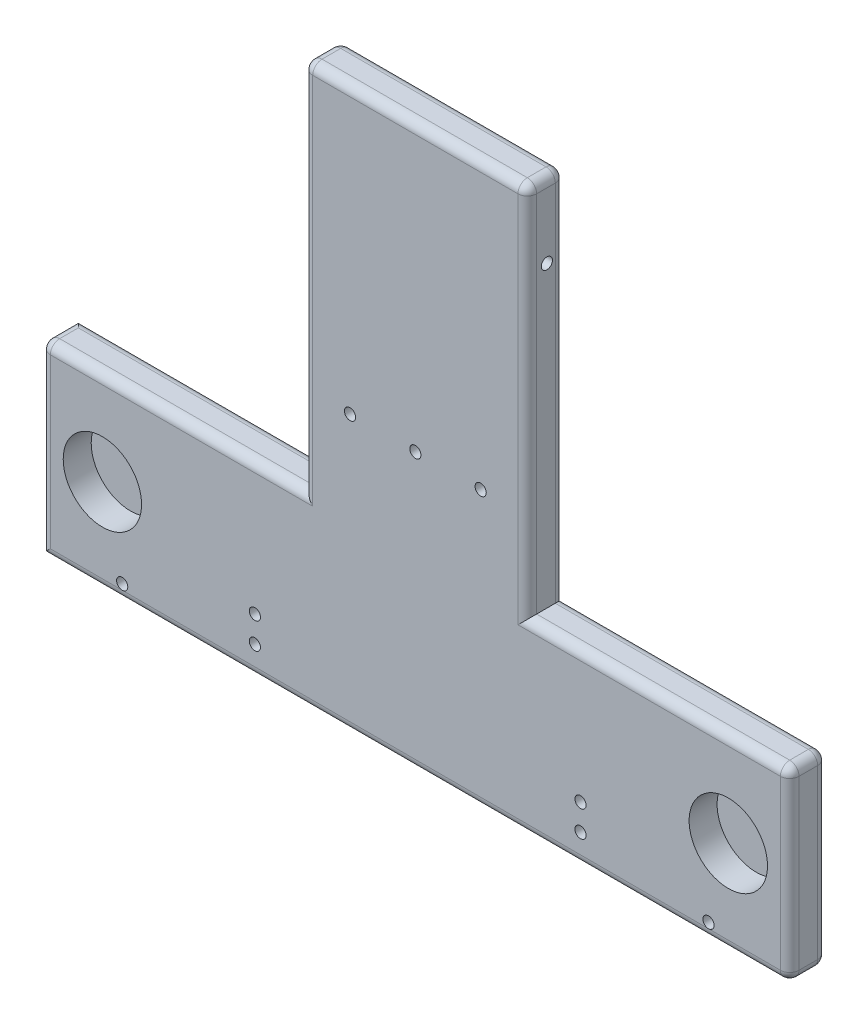
SolidWorks part; units mm, degrees
ref_plane "Front Plane" through (0, 0, 0) normal (0, 0, 1) x (1, 0, 0)
ref_plane "Top Plane" through (0, 0, 0) normal (0, 1, 0) x (1, 0, 0)
ref_plane "Right Plane" through (0, 0, 0) normal (1, 0, 0) x (0, 0, -1)
sketch "Sketch1" plane through (0, 0, 0) normal (0, 0, 1) x (1, 0, 0)
  line L0 (0, 0) -> (0, 190.5941) construction
  line L1 (-200.6, -50) -> (200.6, -50)
  line L2 (-200.6, -50) -> (-200.6, 50)
  line L3 (-200.6, 50) -> (-60, 50)
  line L4 (200.6, -50) -> (200.6, 50)
  line L5 (-200.6, -50) -> (200.6, 50) construction
  line L6 (-200.6, 50) -> (200.6, -50) construction
  line L7 (60, 50) -> (200.6, 50)
  line L8 (-60, 250) -> (60, 250)
  line L9 (-60, 250) -> (-60, 50)
  line L11 (60, 250) -> (60, 50)
  line L12 (-60, 250) -> (60, 50) construction
  line L13 (-60, 50) -> (60, 250) construction
  point P0 (0, 0)
  point P8 (0, 150)
  dimension "D1" = 100
  dimension "D2" = 401.2
  dimension "D3" = 200
  dimension "D4" = 120
extrude "Boss-Extrude1" add sketch "Sketch1" along normal blind 20
sketch "Sketch2" plane through (0, 0, 20) normal (0, 0, 1) x (1, 0, 0)
  line L0 (0, 250) -> (0, -50) construction
  line L1 (60, 250) -> (-60, 250) construction
  line L2 (-200.6, -50) -> (200.6, -50) construction
  line L3 (0, 0) -> (200.6, 0) construction
  line L4 (200.6, -50) -> (200.6, 50) construction
  circle A0 centre (167.7, 0) radius 21
  circle A1 centre (-167.7, 0) radius 21
  dimension "D1" = 42
  dimension "D2" = 167.7
extrude "Cut-Extrude1" cut sketch "Sketch2" against normal blind 15
sketch "Sketch3" plane through (0, 0, 20) normal (0, 0, 1) x (1, 0, 0)
  circle A0 centre (-35, 97.7532) radius 3
  circle A1 centre (35, 97.7532) radius 3
  circle A2 centre (0, 97.7532) radius 3
extrude "Cut-Extrude2" cut sketch "Sketch3" against normal blind 8
cosmetic thread "Cosmetic Thread1" parameters "D2"=10
cosmetic thread "Cosmetic Thread2" parameters "D2"=10
cosmetic thread "Cosmetic Thread3" parameters "D2"=10
sketch "Sketch4" plane through (0, 0, 20) normal (0, 0, 1) x (1, 0, 0)
  circle A0 centre (-86, -20.5) radius 3
  circle A1 centre (88.5, -20.5) radius 3
  circle A2 centre (88.5, -34.5) radius 3
  circle A3 centre (-86, -34.5) radius 3
extrude "Cut-Extrude3" cut sketch "Sketch4" against normal blind 15
cosmetic thread "Cosmetic Thread4" parameters "D2"=10
cosmetic thread "Cosmetic Thread5" parameters "D2"=10
cosmetic thread "Cosmetic Thread6" parameters "D2"=10
cosmetic thread "Cosmetic Thread7" parameters "D2"=10
sketch "Sketch5" plane through (0, 0, 20) normal (0, 0, 1) x (1, 0, 0)
  line L0 (167.7, 0) -> (167.6, -20.9998) construction
  line L1 (-200.6, -50) -> (200.6, -50) construction
  line L2 (167.7, 0) -> (160.0879, -42) construction
  line L3 (167.6, -20.9998) -> (200.6, -20.9998) construction
  line L4 (200.6, -50) -> (200.6, 50) construction
  circle A1 centre (157.0879, -42) radius 3
  circle A2 centre (167.7, 0) radius 21 construction
  dimension "D1" = 6
  dimension "D4" = 10
  dimension "D2" = 20.9998
  dimension "D3" = 8
extrude "Cut-Extrude4" cut sketch "Sketch5" against normal blind 20
cosmetic thread "Cosmetic Thread9" parameters "D2"=10
mirror "Mirror2" about plane through (0, 0, 0) normal (1, 0, 0) of "Cut-Extrude4"
cosmetic thread "Cosmetic Thread8" parameters "D2"=10
cosmetic thread "Cosmetic Thread10" parameters "D2"=10
fillet "Fillet1" radius 5 20 edges at (0, -50, 0) (0, -50, 20) (200.6, -50, 10) (200.6, 0, 0) (-200.6, 0, 20) (-200.6, 50, 10) (-130.3, 50, 0) (-60, 250, 10) (0, 250, 0) (60, 250, 10) (60, 150, 0) (130.3, 50, 0) (200.6, 50, 10) (200.6, 0, 20) (130.3, 50, 20) (60, 150, 20) (0, 250, 20) (-60, 150, 20) (-130.3, 50, 20) (-60, 150, 0)
sketch "Sketch6" plane through (-60, 0, 0) normal (-1, 0, 0) x (0, 0, 1)
  line L0 (20, 245) -> (20, 45) construction
  line L1 (5, 250) -> (15, 250) construction
  circle A2 centre (9.525, 210) radius 3
  dimension "D1" = 6
  dimension "D2" = 10.475
  dimension "D3" = 40
extrude "Cut-Extrude7" cut sketch "Sketch6" against normal blind 10 contours A2
cosmetic thread "Cosmetic Thread13" parameters "D2"=10
mirror "Mirror3" about plane through (0, 0, 0) normal (1, 0, 0) of "Cut-Extrude7"
cosmetic thread "Cosmetic Thread14" parameters "D2"=10
equation "\"D2@Sketch2\" = \"CORabd\""
equation "\"D1@Boss-Extrude1\" = \"hipMember_T\""
equation "\"D2@Sketch1\" = \"width1\""
equation "\"width1\" = 0.4012m"
equation "\"CORabd\" = 0.1677m"
equation "\"hipMember_T\" = 0.0200m"
equation "\"Adduction angle\"= 10deg"
equation "\"Width 1\" = 0.4m'Larger Width"
